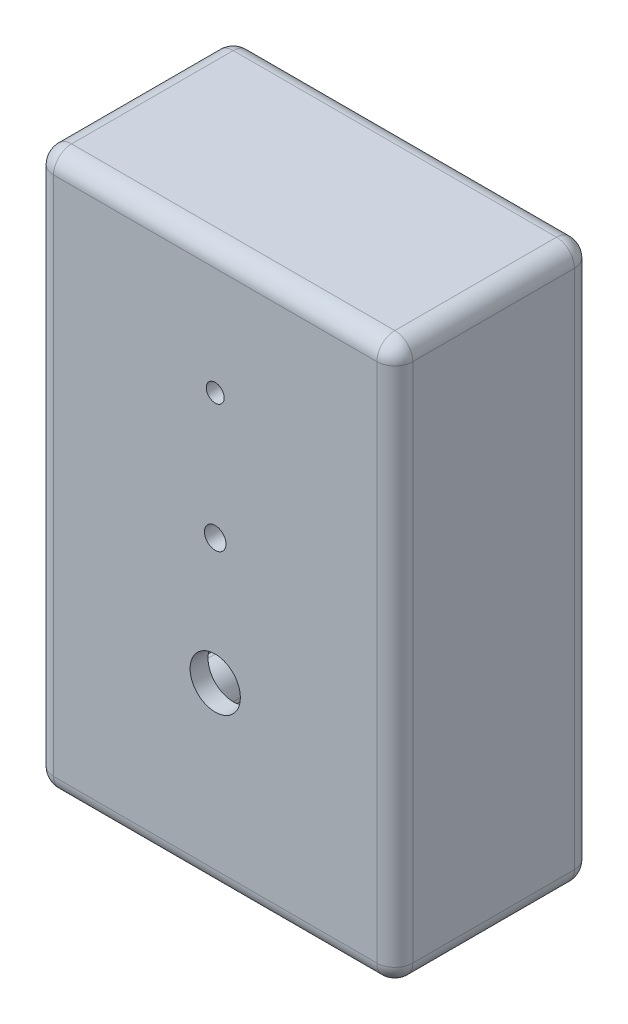
SolidWorks part; units mm, degrees
ref_plane "Front Plane" through (0, 0, 0) normal (0, 0, 1) x (1, 0, 0)
ref_plane "Top Plane" through (0, 0, 0) normal (0, 1, 0) x (1, 0, 0)
ref_plane "Right Plane" through (0, 0, 0) normal (1, 0, 0) x (0, 0, -1)
sketch "Sketch6" plane through (0, 0, 0) normal (0, 0, 1) x (1, 0, 0)
  line L1 (-50, -77.5) -> (50, -77.5)
  line L2 (-50, -77.5) -> (-50, 77.5)
  line L3 (-50, 77.5) -> (50, 77.5)
  line L4 (50, -77.5) -> (50, 77.5)
  line L5 (-50, -77.5) -> (50, 77.5) construction
  line L6 (-50, 77.5) -> (50, -77.5) construction
  point P0 (0, 0)
  dimension "D1" = 100
  dimension "D2" = 155
extrude "Boss-Extrude5" add sketch "Sketch6" along normal blind 55
fillet "Fillet2" radius 5 12 edges at (0, -77.5, 55) (-50, 0, 55) (0, 77.5, 55) (50, 0, 55) (-50, -77.5, 27.5) (50, -77.5, 27.5) (-50, 77.5, 27.5) (50, 77.5, 27.5) (0, 77.5, 0) (-50, 0, 0) (0, -77.5, 0) (50, 0, 0)
shell "Shell3" thickness 5 removed face at (0, 0, 0)
sketch "Sketch7" plane through (0, 0, 50) normal (0, 0, -1) x (-1, 0, 0)
  line L0 (0, 0) -> (0, -72.5) construction
  line L1 (-45, 72.5) -> (-37, 72.5)
  line L2 (-45, 72.5) -> (-45, 64.5)
  line L3 (-45, 64.5) -> (-44, 64.5)
  line L4 (-37, 72.5) -> (-37, 71.5)
  line L5 (45, -72.5) -> (-45, -72.5) construction
  line L6 (0, 0) -> (50, 0) construction
  line L7 (50, 72.5) -> (50, -72.5) construction
  line L8 (45, 72.5) -> (37, 72.5)
  line L9 (45, 72.5) -> (45, 64.5)
  line L10 (45, 64.5) -> (44, 64.5)
  line L11 (37, 72.5) -> (37, 71.5)
  line L12 (-45, -64.5) -> (-44, -64.5)
  line L13 (-37, -72.5) -> (-37, -71.5)
  line L14 (-45, -72.5) -> (-37, -72.5)
  line L15 (-45, -72.5) -> (-45, -64.5)
  line L16 (45, -72.5) -> (45, -64.5)
  line L17 (45, -64.5) -> (44, -64.5)
  line L18 (37, -72.5) -> (37, -71.5)
  line L19 (45, -72.5) -> (37, -72.5)
  arc A1 (44, 64.5) -> (37, 71.5) centre (44, 71.5) cw
  arc A2 (-37, 71.5) -> (-44, 64.5) centre (-44, 71.5) cw
  arc A3 (-37, -71.5) -> (-44, -64.5) centre (-44, -71.5) ccw
  arc A4 (44, -64.5) -> (37, -71.5) centre (44, -71.5) ccw
  circle A5 centre (-42, 69.5) radius 2.1 construction
  point P19 (37, 64.5)
  point P22 (-37, 64.5)
  dimension "D3" = 7
  dimension "D4" = 4.2
  dimension "D1" = 8
  dimension "D2" = 8
  dimension "D5" = 3
  dimension "D6" = 3
extrude "Boss-Extrude6" add sketch "Sketch7" along normal blind 45
sketch "Sketch8" plane through (0, 0, 5) normal (0, 0, -1) x (-1, 0, 0)
  line L0 (-37, 72.5) -> (-45, 72.5) construction
  line L1 (-45, 72.5) -> (-45, 64.5) construction
  line L2 (0, 0) -> (0, -72.5) construction
  line L3 (37, -72.5) -> (-37, -72.5) construction
  line L4 (0, 0) -> (45, 0) construction
  line L5 (45, 64.5) -> (45, -64.5) construction
  circle A0 centre (-42, 69.5) radius 2.1
  circle A1 centre (42, 69.5) radius 2.1
  circle A2 centre (42, -69.5) radius 2.1
  circle A3 centre (-42, -69.5) radius 2.1
  dimension "D1" = 4.2
  dimension "D2" = 3
  dimension "D3" = 3
extrude "Cut-Extrude1" cut sketch "Sketch8" against normal blind 6.5
sketch "Sketch9" plane through (0, 0, 55) normal (0, 0, 1) x (1, 0, 0)
  line L0 (0, 72.5) -> (0, -72.5) construction
  line L1 (45, 72.5) -> (-45, 72.5) construction
  line L2 (-45, -72.5) -> (45, -72.5) construction
  circle A0 centre (0, 42.5) radius 2.5
  circle A1 centre (0, 7.5) radius 3
  circle A2 centre (0, -27.5) radius 7
  dimension "D1" = 5
  dimension "D2" = 6
  dimension "D3" = 14
  dimension "D4" = 30
  dimension "D5" = 65
  dimension "D6" = 100
extrude "Cut-Extrude2" cut sketch "Sketch9" against normal through all
sketch "Sketch10" plane through (0, -77.5, 0) normal (0, -1, 0) x (1, 0, 0)
  line L0 (0, 50) -> (0, 0) construction
  line L1 (45, 50) -> (-45, 50) construction
  line L2 (0, 50) -> (9, 50) construction
  line L3 (-3.5, 50) -> (3.5, 50)
  line L4 (5.5, 48) -> (5.5, 47.8)
  line L5 (3.5, 45.8) -> (-3.5, 45.8)
  line L6 (-5.5, 48) -> (-5.5, 47.8)
  arc A0 (5.5, 48) -> (3.5, 50) centre (3.5, 48) ccw
  arc A1 (5.5, 47.8) -> (3.5, 45.8) centre (3.5, 47.8) cw
  arc A2 (-5.5, 47.8) -> (-3.5, 45.8) centre (-3.5, 47.8) ccw
  arc A3 (-5.5, 48) -> (-3.5, 50) centre (-3.5, 48) cw
  point P11 (5.5, 50)
  point P14 (5.5, 45.8)
  point P16 (0, 45.8)
  dimension "D4" = 2
  dimension "D1" = 9
  dimension "D2" = 5.5
  dimension "D3" = 4.2
extrude "Cut-Extrude3" cut sketch "Sketch10" against normal up to next
sketch "Sketch13" plane through (0, -72.5, 0) normal (0, 1, 0) x (1, 0, 0)
  line L3 (-5.5, -48) -> (-5.5, -47.8) construction
  line L4 (-3.5, -45.8) -> (3.5, -45.8) construction
  line L5 (5.5, -47.8) -> (5.5, -48) construction
  line L6 (5.5, -47.8) -> (5.5, -48)
  line L7 (-3.5, -45.8) -> (3.5, -45.8)
  line L8 (-5.5, -48) -> (-5.5, -47.8)
  line L9 (-3.5, -50) -> (3.5, -50)
  line L10 (0, -50) -> (0, -48.8) construction
  line L11 (-5.333, -48.8) -> (-10.333, -48.8)
  line L12 (-10.333, -48.8) -> (-10.333, -50)
  line L13 (-3.5, -50) -> (-45, -50) construction
  line L14 (-10.333, -50) -> (-3.5, -50)
  line L15 (10.333, -50) -> (3.5, -50)
  line L16 (10.333, -48.8) -> (10.333, -50)
  line L17 (5.333, -48.8) -> (10.333, -48.8)
  arc A4 (-5.5, -48) -> (-3.5, -50) centre (-3.5, -48) ccw construction
  arc A5 (-3.5, -45.8) -> (-5.5, -47.8) centre (-3.5, -47.8) ccw construction
  arc A6 (5.5, -47.8) -> (3.5, -45.8) centre (3.5, -47.8) ccw construction
  arc A7 (3.5, -50) -> (5.5, -48) centre (3.5, -48) ccw construction
  arc A8 (5.333, -48.8) -> (5.5, -48) centre (3.5, -48) ccw
  arc A9 (5.5, -47.8) -> (3.5, -45.8) centre (3.5, -47.8) ccw
  arc A10 (-3.5, -45.8) -> (-5.5, -47.8) centre (-3.5, -47.8) ccw
  arc A11 (-5.5, -48) -> (-5.333, -48.8) centre (-3.5, -48) ccw
  dimension "D1" = 1.2
  dimension "D2" = 5
  dimension "D3" = 1.2
extrude "Cut-Extrude4" cut sketch "Sketch13" against normal blind 3
sketch "Sketch14" plane through (0, 0, 50) normal (0, 0, -1) x (-1, 0, 0)
  line L0 (0, -48.5) -> (0, -74.5) construction
  line L1 (45, -77.5) -> (-45, -77.5) construction
  line L2 (0, -74.5) -> (0, -48.5) construction
  line L4 (7.5, -46.6) -> (7.5, -46.5)
  line L5 (7.5, -46.5) -> (9.5, -46.5) construction
  line L6 (0, -74.5) -> (9.5, -74.5)
  line L7 (9.5, -46.5) -> (9.5, -74.5) construction
  line L10 (-7.5, -46.6) -> (7.5, -46.5)
  line L11 (-5.6, -48.5) -> (5.6, -48.5)
  arc A0 (7.5, -46.6) -> (5.6, -48.5) centre (5.6, -46.6) cw
  arc A1 (-7.5, -46.6) -> (-5.6, -48.5) centre (-5.6, -46.6) ccw
  point P13 (7.5, -48.5)
  point P15 (0, -46.5)
  dimension "D6" = 1.9
  dimension "D1" = 3
  dimension "D2" = 26
  dimension "D3" = 9.5
  dimension "D4" = 2
  dimension "D5" = 2
  dimension "D7" = 7.5
extrude "Boss-Extrude7" add sketch "Sketch14" along normal blind 3 contours L10 A1 L11 A0 L4 region at (-0.0677, -47.494, 50)
